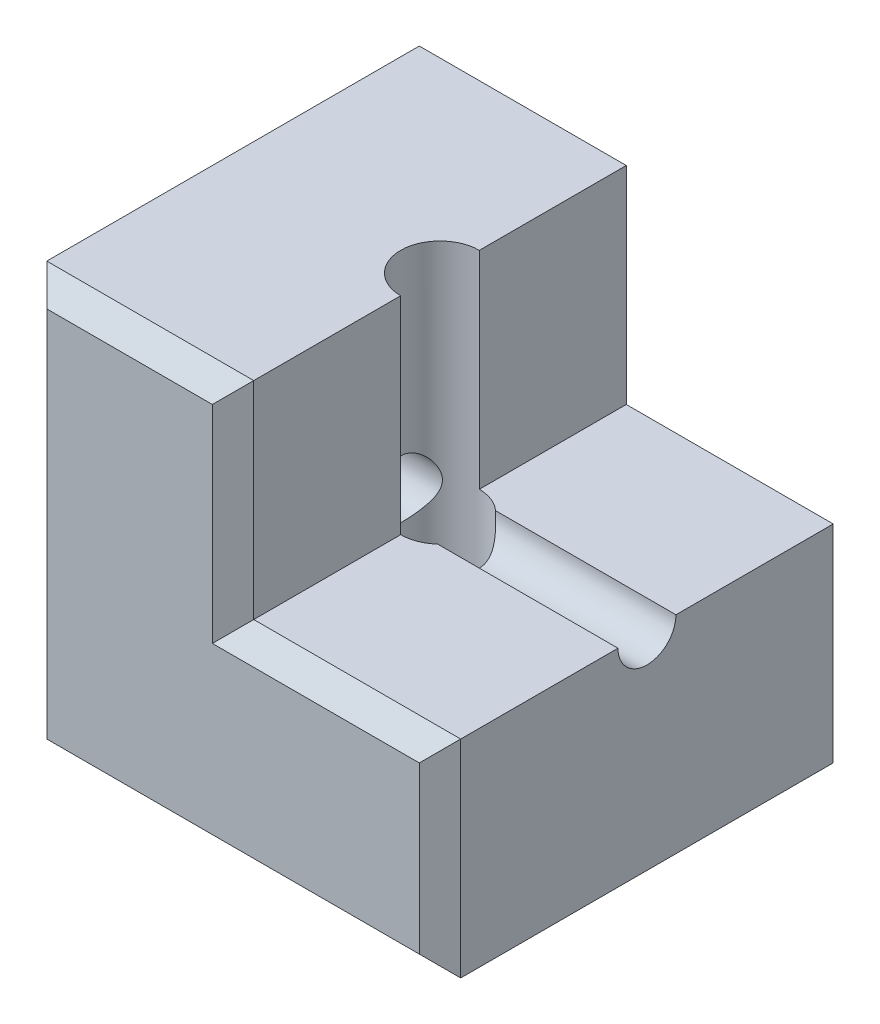
SolidWorks part; units mm, degrees
ref_plane "Front Plane" through (0, 0, 0) normal (0, 0, 1) x (1, 0, 0)
ref_plane "Top Plane" through (0, 0, 0) normal (0, 1, 0) x (1, 0, 0)
ref_plane "Right Plane" through (0, 0, 0) normal (1, 0, 0) x (0, 0, -1)
sketch "Sketch2" plane through (0, 0, 0) normal (0, 0, 1) x (1, 0, 0)
  line L0 (0, 20) -> (0, 0)
  line L1 (0, 0) -> (20, 0)
  line L2 (20, 0) -> (20, 10)
  line L3 (20, 10) -> (10, 10)
  line L4 (10, 10) -> (10, 20)
  line L5 (10, 20) -> (0, 20)
  dimension "D1" = 20
  dimension "D2" = 10
extrude "Boss-Extrude2" add sketch "Sketch2" along normal blind 20
sketch "Sketch3" plane through (0, 0, 0) normal (-1, 0, 0) x (0, 0, 1)
  line L0 (20, 20) -> (0, 20) construction
  circle A0 centre (10, 10) radius 1.4
  point P4 (10, 20)
  point P7 (0, 0)
  point P9 (0, 0)
  dimension "D1" = 2.8
extrude "Cut-Extrude1" cut sketch "Sketch3" against normal through all
ref_plane "Plane1" through (0, 3, 0) normal (0, -1, 0) x (-1, 0, 0)
sketch "Sketch4" plane through (0, 3, 0) normal (0, -1, 0) x (-1, 0, 0)
  line L0 (-20, -20) -> (-20, 0) construction
  circle A0 centre (-10, -10) radius 1.9
  point P2 (0, 0)
  point P4 (0, 0)
  point P7 (-20, -10)
  dimension "D1" = 3.8
extrude "Cut-Extrude2" cut sketch "Sketch4" against normal through all both and the other way through all
sketch "Sketch5" plane through (0, 3, 0) normal (0, -1, 0) x (-1, 0, 0)
  line L0 (-12.75, -5.5) -> (-14.2237, 0)
  line L1 (-12.75, -14.5) -> (-7.25, -14.5)
  line L2 (-12.75, -14.5) -> (-12.75, -5.5)
  line L3 (-12.75, -5.5) -> (-7.25, -5.5) construction
  line L4 (-7.25, -14.5) -> (-7.25, -5.5)
  line L5 (-10, -5.5) -> (-10, -14.5) construction
  line L6 (-12.75, -10) -> (-7.25, -10) construction
  line L7 (-14.2237, 0) -> (-5.7763, 0)
  line L8 (-5.7763, 0) -> (-7.25, -5.5)
  point P0 (-10, -10)
  point P5 (0, 0)
  dimension "D1" = 5.5
  dimension "D2" = 9
  dimension "D3" = 15
extrude "Cut-Extrude3" cut sketch "Sketch5" against normal blind 3
chamfer "Chamfer1" distance 1 angle 45 2 edges at (10, 3, 0) (10, 6, 0)
chamfer "Chamfer2" distance 1 angle 45 6 edges at (10, 15, 20) (15, 10, 20) (20, 5, 20) (10, 0, 20) (0, 10, 20) (5, 20, 20)
chamfer "Chamfer5" distance 1 angle 45 6 edges at (20, 5, 0) (10, 0, 0) (0, 10, 0) (5, 20, 0) (10, 15, 0) (15, 10, 0)
